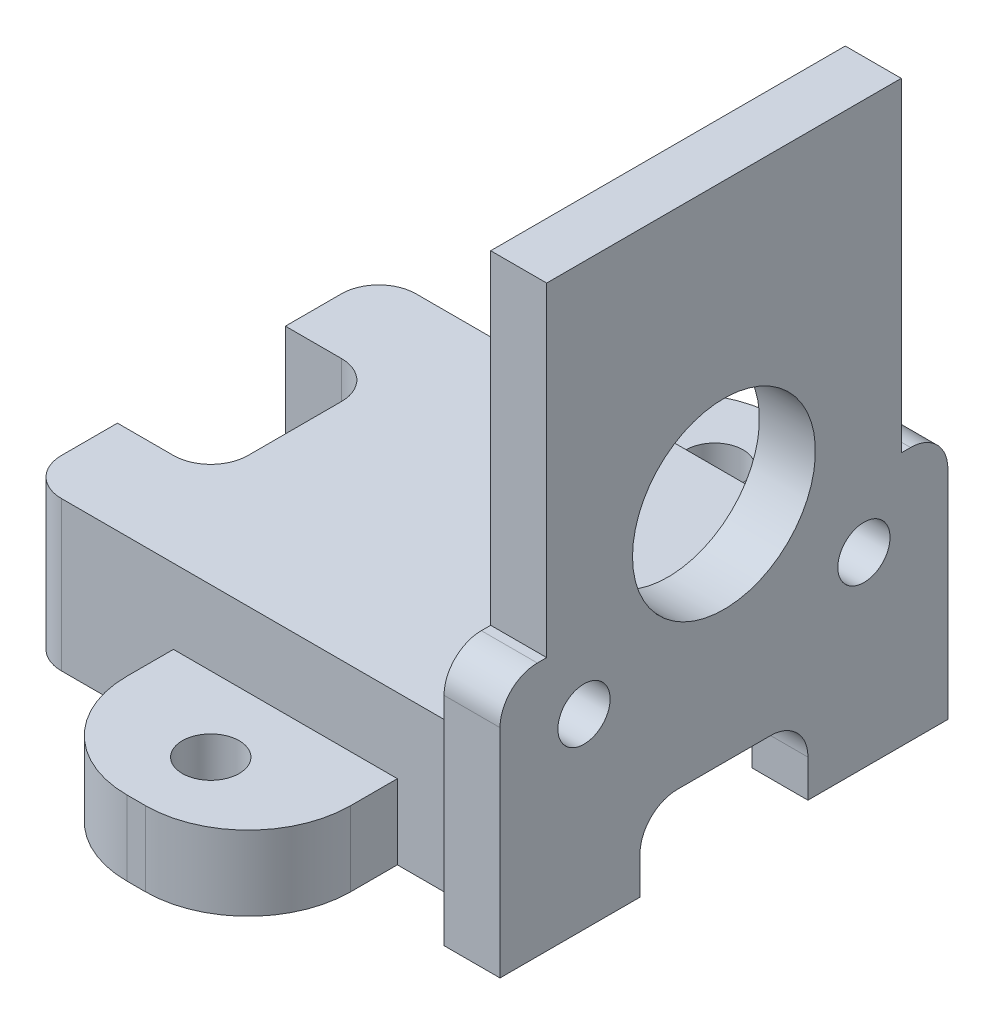
SolidWorks part; units mm, degrees
ref_plane "Front Plane" through (0, 0, 0) normal (0, 0, 1) x (1, 0, 0)
ref_plane "Top Plane" through (0, 0, 0) normal (0, 1, 0) x (1, 0, 0)
ref_plane "Right Plane" through (0, 0, 0) normal (1, 0, 0) x (0, 0, -1)
sketch "Sketch1" plane through (0, 0, 0) normal (0, 1, 0) x (1, 0, 0)
  line L0 (-1, -3) -> (23, -3)
  line L1 (0, 0) -> (22, 0)
  line L2 (0, 0) -> (0, 13)
  line L3 (0, 13) -> (22, 13)
  line L4 (22, 0) -> (22, 13)
  line L5 (25, -1) -> (25, 14)
  line L6 (-1, 16) -> (23, 16)
  line L7 (-3, -1) -> (-3, 14)
  line L8 (-3, -3) -> (25, -3) construction
  line L9 (25, -3) -> (25, 16) construction
  line L10 (-3, 16) -> (25, 16) construction
  line L11 (-3, -3) -> (-3, 16) construction
  line L12 (23, -3) -> (25, -3)
  line L13 (25, -3) -> (25, -1)
  line L14 (25, 16) -> (23, 16)
  line L15 (25, 16) -> (25, 14)
  arc A2 (-1, 16) -> (-3, 14) centre (-1, 14) ccw
  arc A3 (-1, -3) -> (-3, -1) centre (-1, -1) cw
  dimension "D1" = 22
  dimension "D2" = 13
  dimension "D3" = 3
extrude "Boss-Extrude1" add sketch "Sketch1" along normal blind 6
sketch "Sketch2" plane through (0, 6, 0) normal (0, 1, 0) x (1, 0, 0)
  line L0 (25, 14) -> (25, -1)
  line L1 (23, -3) -> (-1, -3)
  line L2 (-3, -1) -> (-3, 14)
  line L3 (-1, 16) -> (23, 16)
  line L4 (25, 16) -> (-1, 16) construction
  line L5 (23, -3) -> (25, -3)
  line L6 (25, -3) -> (25, -1)
  line L7 (25, 14) -> (25, 16)
  line L8 (25, 16) -> (23, 16)
  arc A1 (-1, -3) -> (-3, -1) centre (-1, -1) cw
  arc A2 (-3, 14) -> (-1, 16) centre (-1, 14) cw
extrude "Boss-Extrude2" add sketch "Sketch2" along normal blind 2
sketch "Sketch3" plane through (0, 0, 0) normal (0, -1, 0) x (1, 0, 0)
  line L0 (-1, 3) -> (25, 3) construction
  line L1 (5, 3) -> (17, 3)
  line L2 (5, 3) -> (5, 5.5)
  line L3 (10.5, 11) -> (11.5, 11)
  line L4 (17, 3) -> (17, 5.5)
  line L5 (25, -16) -> (-1, -16) construction
  line L6 (17, -16) -> (5, -16)
  line L7 (17, -16) -> (17, -18.5)
  line L8 (11.5, -24) -> (10.5, -24)
  line L9 (5, -16) -> (5, -18.5)
  line L10 (25, 3) -> (25, -16) construction
  line L11 (-3, -14) -> (-3, 1) construction
  arc A0 (17, -18.5) -> (11.5, -24) centre (11.5, -18.5) cw
  arc A1 (10.5, -24) -> (5, -18.5) centre (10.5, -18.5) cw
  arc A2 (5, 5.5) -> (10.5, 11) centre (10.5, 5.5) cw
  arc A3 (11.5, 11) -> (17, 5.5) centre (11.5, 5.5) cw
  point P16 (17, -17.25)
  point P19 (17, -24)
  point P26 (17, 11)
  dimension "D7" = 5.5
  dimension "D1" = 8
  dimension "D2" = 8
  dimension "D3" = 8
  dimension "D4" = 8
  dimension "D5" = 8
  dimension "D6" = 8
extrude "Boss-Extrude3" add sketch "Sketch3" against normal up to surface (8 mm away) up to face at (6.8619, 8, -6.5)
sketch "Sketch4" plane through (0, 0, 0) normal (0, -1, 0) x (-1, 0, 0)
  line L0 (-17, 18.5) -> (-17, 16) construction
  line L2 (-10.5, 24) -> (-11.5, 24) construction
  line L3 (-11.5, -11) -> (-10.5, -11) construction
  line L4 (-5, -5.5) -> (-5, -3) construction
  circle A0 centre (-11, 20) radius 1.525
  circle A1 centre (-11, -7) radius 1.524
  point P9 (-11, 24)
  dimension "D1" = 3.048
  dimension "D2" = 3.05
  dimension "D3" = 6
  dimension "D4" = 4
  dimension "D5" = 4
  dimension "D6" = 6
extrude "Cut-Extrude1" cut sketch "Sketch4" against normal through all
sketch "Sketch5" plane through (25, 0, 0) normal (1, 0, 0) x (0, 0, -1)
  line L0 (-3, 0) -> (16, 0) construction
  line L1 (11, 0) -> (2, 0)
  line L2 (11, 0) -> (11, 4)
  line L3 (11, 4) -> (2, 4)
  line L4 (2, 0) -> (2, 4)
  line L5 (-3, 8) -> (-3, 0) construction
  line L6 (16, 8) -> (16, 0) construction
  line L7 (-3, 8) -> (16, 8) construction
  dimension "D1" = 5
  dimension "D2" = 5
  dimension "D3" = 4
extrude "Cut-Extrude2" cut sketch "Sketch5" against normal through all
fillet "Fillet1" radius 2 4 edges at (-1.5, 4, -2) (-1.5, 4, -11) (23.5, 4, -11) (23.5, 4, -2)
sketch "Sketch6" plane through (0, 8, 0) normal (0, 1, 0) x (1, 0, 0)
  line L0 (-1, -3) -> (5, -3) construction
  line L1 (17, 16) -> (5, 16)
  line L2 (17, 16) -> (17, 29.009)
  line L3 (17, 29.009) -> (5, 29.009)
  line L4 (5, 16) -> (5, 29.009)
  line L5 (19.0682, -16.009) -> (3.2299, -16.009)
  line L6 (19.0682, -16.009) -> (19.0682, -3)
  line L7 (19.0682, -3) -> (3.2299, -3)
  line L8 (3.2299, -16.009) -> (3.2299, -3)
extrude "Cut-Extrude3" cut sketch "Sketch6" against normal blind 4
sketch "Sketch7" plane through (0, 8, 0) normal (0, 1, 0) x (1, 0, 0)
  line L0 (-1, -3) -> (25, -3) construction
  line L1 (23, 16) -> (22, 16)
  line L2 (25, 14) -> (25, -1)
  line L3 (23, -3) -> (22, -3)
  line L4 (22, 16) -> (22, -3)
  line L5 (25, 16) -> (-1, 16) construction
  line L6 (25, -3) -> (25, 16) construction
  line L7 (23, -3) -> (25, -3)
  line L8 (25, -3) -> (25, -1)
  line L9 (25, 14) -> (25, 16)
  line L10 (25, 16) -> (23, 16)
  point P12 (25, 16)
  dimension "D1" = 3
extrude "Boss-Extrude4" add sketch "Sketch7" along normal blind 23
sketch "Sketch8" plane through (0, 8, 0) normal (0, 1, 0) x (1, 0, 0)
  line L0 (-3, 14) -> (-3, -1) construction
  line L1 (-3, 2) -> (0, 2)
  line L2 (-3, 2) -> (-3, 11)
  line L3 (-3, 11) -> (0, 11)
  line L4 (2, 4) -> (2, 9)
  line L5 (22, 16) -> (-1, 16) construction
  line L6 (-1, -3) -> (22, -3) construction
  arc A0 (0, 2) -> (2, 4) centre (0, 4) ccw
  arc A1 (0, 11) -> (2, 9) centre (0, 9) cw
  point P12 (2, 2)
  dimension "D4" = 2
  dimension "D1" = 5
  dimension "D2" = 5
  dimension "D3" = 5
extrude "Cut-Extrude4" cut sketch "Sketch8" against normal blind 23
sketch "Sketch9" plane through (22, 0, 0) normal (-1, 0, 0) x (0, 0, 1)
  line L2 (-16, 31) -> (3, 31) construction
  line L4 (-16, 8) -> (3, 8) construction
  circle A0 centre (-6.5, 16) radius 4.9
  point P10 (-6.5, 31)
  dimension "D1" = 9.8
  dimension "D2" = 8
extrude "Cut-Extrude6" cut sketch "Sketch9" against normal blind 23 contours A0
sketch "Sketch10" plane through (22, 0, 0) normal (-1, 0, 0) x (0, 0, 1)
  line L0 (-16, 31) -> (-16, 8) construction
  line L1 (-16, 8) -> (3, 8) construction
  line L2 (3, 31) -> (3, 8) construction
  circle A0 centre (-14, 10) radius 1.4
  circle A1 centre (1, 10) radius 1.4
  dimension "D5" = 2.8
  dimension "D6" = 2.8
  dimension "D1" = 2
  dimension "D2" = 2
  dimension "D3" = 2
  dimension "D4" = 2
extrude "Cut-Extrude7" cut sketch "Sketch10" against normal blind 23
sketch "Sketch11" plane through (25, 0, 0) normal (1, 0, 0) x (0, 0, -1)
  line L0 (-5.5, 4) -> (-5.5, 0) construction
  line L1 (-3, 0) -> (-5.5, 0)
  line L2 (-3, 0) -> (-3, 13.6179)
  line L3 (-3, 13.6179) -> (-3.5, 13.6179)
  line L4 (-5.5, 0) -> (-5.5, 11.6179)
  line L5 (18.5, 4) -> (18.5, 0) construction
  line L6 (16, 0) -> (18.5, 0)
  line L7 (16, 0) -> (16, 13.6179)
  line L8 (16, 13.6179) -> (16.5, 13.6179)
  line L9 (18.5, 0) -> (18.5, 11.6179)
  arc A0 (-3.5, 13.6179) -> (-5.5, 11.6179) centre (-3.5, 11.6179) ccw
  arc A1 (16.5, 13.6179) -> (18.5, 11.6179) centre (16.5, 11.6179) cw
  dimension "D1" = 2
  dimension "D2" = 2
extrude "Boss-Extrude5" add sketch "Sketch11" against normal up to surface (3 mm away) up to face at (22, 10, 2.4)
fillet "Fillet2" radius 2.5 1 edges at (22, 4, 3)
fillet "Fillet3" radius 2.5 1 edges at (22, 4, -16)
